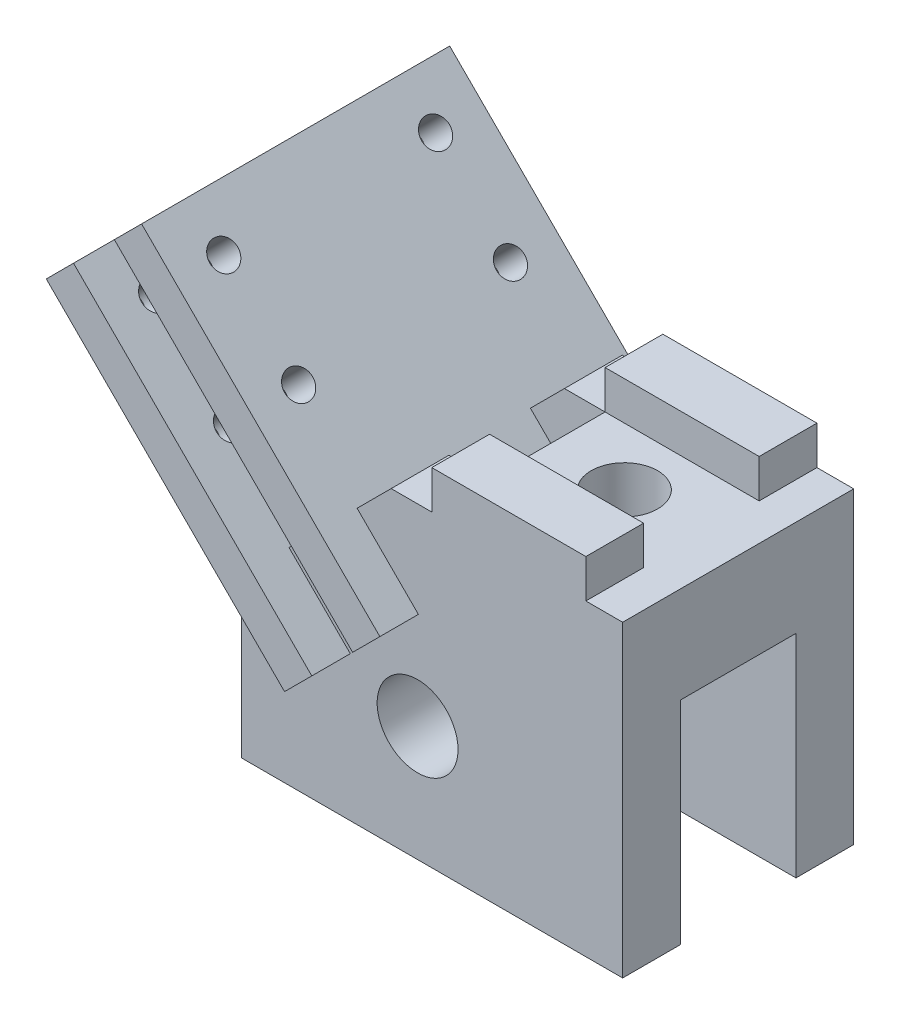
SolidWorks part; units mm, degrees
material "ABS"
ref_plane "Front Plane" through (0, 0, 0) normal (0, 0, 1) x (1, 0, 0)
ref_plane "Top Plane" through (0, 0, 0) normal (0, 1, 0) x (1, 0, 0)
ref_plane "Right Plane" through (0, 0, 0) normal (1, 0, 0) x (0, 0, -1)
sketch "Sketch1" plane through (0, 0, 0) normal (0, 0, 1) x (1, 0, 0)
  line L0 (12.7272, 5.3941) -> (4.9497, 13.1716) construction
  line L1 (9.8891, 16) -> (9.8891, 11) construction
  line L2 (9.8891, 11) -> (17.8891, 11) construction
  line L3 (17.8891, 11) -> (17.8891, 16) construction
  line L4 (13.8891, 18) -> (13.8891, 8) construction
  line L20 (0, 8.2218) -> (7.7782, 16)
  line L21 (0, 0) -> (0, 8.2218)
  line L22 (0, 0) -> (19.8, 0)
  line L23 (19.8, 0) -> (19.8, 16)
  line L24 (19.8, 16) -> (17.8891, 16)
  line L25 (9.8891, 16) -> (9.8891, 18)
  line L26 (9.8891, 18) -> (17.8891, 18)
  line L27 (17.8891, 18) -> (17.8891, 16)
  line L28 (9.8891, 16) -> (7.7782, 16)
  line L29 (2.2754, 13.7246) -> (3.8891, 12.1109) construction
  line L30 (0, 6) -> (19.8, 6) construction
  circle A0 centre (9.1515, 6) radius 2.1
  dimension "D2" = 4.2
  dimension "D3" = 11
  dimension "D6" = 45
  dimension "D7" = 6
  dimension "D8" = 7
  dimension "D4" = 6
  dimension "D9" = 16
  dimension "D10" = 19.8
  dimension "D11" = 2
  dimension "D12" = 8
  dimension "D13" = 5
  dimension "D14" = 10
extrude "Finger Base 1" add sketch "Sketch1" along normal mid plane 12
sketch "Sketch2" plane through (-4.1109, 4.1109, 0) normal (-0.7071, 0.7071, 0) x (0, 0, 1)
  line L0 (0, 16.8137) -> (0, 5.8137) construction
  line L1 (-8, 9.3137) -> (8, 9.3137)
  line L2 (-8, 9.3137) -> (-8, 7.3137)
  line L3 (-8, 7.3137) -> (8, 7.3137)
  line L4 (8, 9.3137) -> (8, 7.3137)
  line L5 (-8, 9.3137) -> (8, 7.3137) construction
  line L6 (-8, 7.3137) -> (8, 9.3137) construction
  line L7 (6, 16.8137) -> (-6, 16.8137) construction
  line L8 (6, 5.8137) -> (-6, 5.8137) construction
  point P0 (0, 8.3137)
  dimension "D1" = 2
  dimension "D2" = 16
  dimension "D3" = 2.5
extrude "Flexure Joint Base" add sketch "Sketch2" along normal blind 13
sketch "Sketch3" plane through (0, 0, 0) normal (0, 0, 1) x (1, 0, 0)
  line L0 (9.1515, 3.9) -> (9.1515, 0)
  line L1 (7.0547, 6.1168) -> (2.4749, 10.6967)
  line L2 (-6.7175, 19.8891) -> (2.4749, 10.6967) construction
  line L3 (13.8891, 18) -> (13.8891, 8) construction
  line L4 (9.1515, 0) -> (19.8, 0)
  line L5 (9.8891, 16) -> (9.8891, 11)
  line L6 (9.8891, 11) -> (19.8, 11)
  line L7 (19.8, 11) -> (19.8, 0)
  line L8 (17.8891, 18) -> (9.8891, 18) construction
  line L9 (12.3891, 8) -> (15.3891, 8) construction
  line L10 (12.3891, 8) -> (12.3891, 18) construction
  line L11 (12.3891, 18) -> (15.3891, 18) construction
  line L12 (15.3891, 18) -> (15.3891, 8) construction
  line L13 (7.7782, 16) -> (9.8891, 16)
  line L14 (9.8891, 16) -> (9.8891, 18)
  line L16 (9.8891, 18) -> (17.8891, 18)
  line L19 (17.8891, 18) -> (17.8891, 16)
  line L20 (17.8891, 16) -> (9.8891, 16)
  line L22 (0, 0) -> (19.8, 0) construction
  line L24 (2.4749, 10.6967) -> (7.7782, 16)
  line L26 (19.8, 0) -> (19.8, 16) construction
  line L27 (19.8, 16) -> (17.8891, 16) construction
  line L28 (19.8, 16) -> (17.8891, 16)
  line L29 (19.8, 16) -> (19.8, 11)
  circle A0 centre (9.1515, 6) radius 2.1 construction
  arc A1 (7.0547, 6.1168) -> (9.1515, 3.9) centre (9.1515, 6) ccw
  dimension "D1" = 3
  dimension "D2" = 10
  dimension "D3" = 5
extrude "Pulley Housing" cut sketch "Sketch3" against normal mid plane 6
sketch "Sketch4" plane through (0, 11, 0) normal (0, -1, 0) x (1, 0, 0)
  line L0 (9.8891, 0) -> (13.8891, 0) construction
  line L2 (9.8891, -3) -> (9.8891, 3) construction
  line L4 (10.5982, 0) -> (12.2436, -2.85)
  line L5 (12.2436, -2.85) -> (15.5345, -2.85)
  line L6 (15.5345, -2.85) -> (17.18, 0)
  line L7 (17.18, 0) -> (15.5345, 2.85)
  line L8 (15.5345, 2.85) -> (12.2436, 2.85)
  line L9 (12.2436, 2.85) -> (10.5982, 0)
  circle A0 centre (13.8891, 0) radius 2.85 construction
  dimension "D1" = 5.7
  dimension "D2" = 4
extrude "M3 Nut" cut sketch "Sketch4" against normal blind 2
sketch "Sketch5" plane through (0, 13, 0) normal (0, -1, 0) x (1, 0, 0)
  line L0 (9.8891, 0) -> (13.8891, 0) construction
  line L2 (9.8891, -3) -> (9.8891, 3) construction
  circle A0 centre (13.8891, 0) radius 1.725
  dimension "D1" = 4
  dimension "D2" = 3.45
extrude "M3 Hole" cut sketch "Sketch5" against normal up to surface (3 mm away) up to face at (16.3668, 16, 0)
sketch "Sketch9" plane through (-4.1109, 4.1109, 0) normal (0.7071, -0.7071, 0) x (0, 0, -1)
  line L1 (-8, 9.3137) -> (-6, 9.3137)
  line L2 (-8, 9.3137) -> (-8, 7.3137)
  line L3 (-8, 7.3137) -> (-6, 7.3137)
  line L4 (-6, 9.3137) -> (-6, 7.3137)
  line L5 (6, 9.3137) -> (8, 9.3137)
  line L6 (6, 9.3137) -> (6, 7.3137)
  line L7 (6, 7.3137) -> (8, 7.3137)
  line L8 (8, 9.3137) -> (8, 7.3137)
extrude "Support Flexure Joint Base " add sketch "Sketch9" along normal blind 4.5
sketch "Sketch10" plane through (6.5858, 6.5858, 0) normal (0.7071, 0.7071, 0) x (0.7071, -0.7071, 0)
  line L0 (-18.8137, -8) -> (-1.3137, -8) construction
  line L1 (-18.8137, -8) -> (-18.8137, 8) construction
  line L2 (0, 0) -> (-18.8137, 0) construction
  circle A0 centre (-16.3137, -5.5) radius 0.725
  circle A1 centre (-10.8137, -5.5) radius 0.725
  circle A2 centre (-10.8137, 5.5) radius 0.725
  circle A3 centre (-16.3137, 5.5) radius 0.725
  dimension "D4" = 1.45
  dimension "D1" = 2.5
  dimension "D2" = 2.5
  dimension "D3" = 8
extrude "Hole For Stiching" cut sketch "Sketch10" against normal through all
sketch "Sketch11" plane through (0, 0, 6) normal (0, 0, 1) x (1, 0, 0)
  line L0 (4.5962, 12.818) -> (6.0104, 11.4038)
  line L1 (7.7782, 16) -> (2.4749, 10.6967) construction
  line L2 (6.0104, 11.4038) -> (7.4246, 12.818)
  line L3 (7.4246, 12.818) -> (6.0104, 14.2322)
  line L4 (-6.7175, 19.8891) -> (5.6569, 7.5147) construction
  line L8 (5.6569, 7.5147) -> (2.4749, 10.6967) construction
  line L9 (5.6569, 7.5147) -> (4.2426, 6.1005) construction
  dimension "D1" = 3
  dimension "D2" = 2
extrude "Cut-Extrude1" cut sketch "Sketch11" against normal through all and the other way through all
surface "Surface-Offset2" parameters "D1"=0
move or copy body "Body-Move/Copy2" bodies to move or copy 117 placed by mates yes
sketch "Sketch25" plane through (10.1213, 10.1213, 0) normal (0.7071, 0.7071, 0) x (0, 0, -1)
  line L0 (-3, 3.8137) -> (3, 3.8137)
surface "Surface-Trim2"
sketch "Sketch31" plane through (8.7071, 8.7071, 0) normal (-0.7071, -0.7071, 0) x (0, 0, 1)
  line L0 (-3, 3.8137) -> (3, 3.8137)
surface "Surface-Fill5"
surface "Surface-Fill6"
